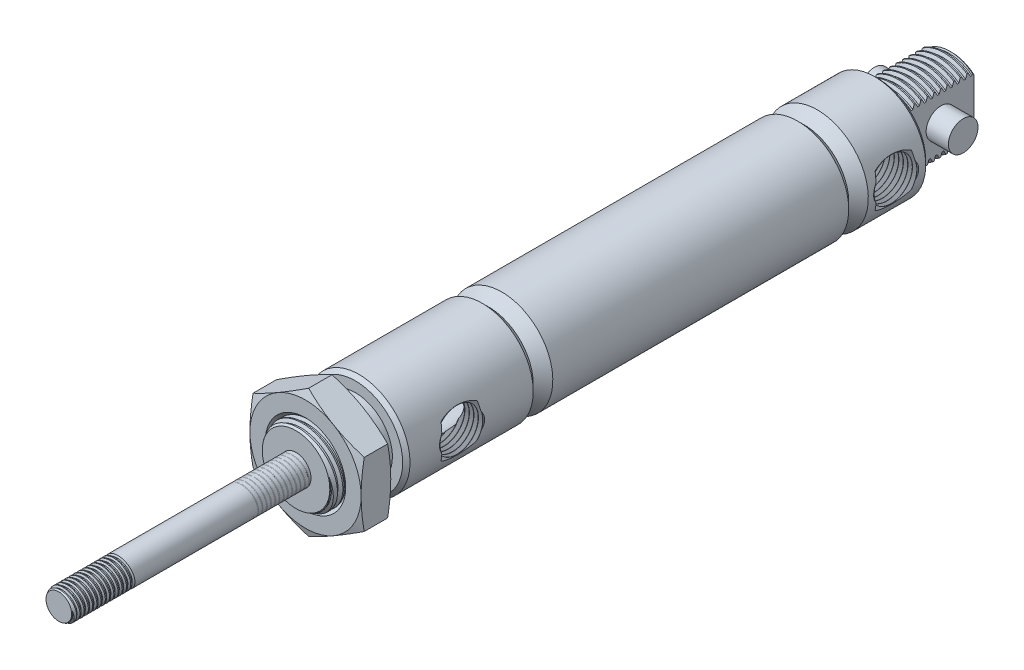
SolidWorks part; units mm, degrees
ref_plane "Front" through (0, 0, 0) normal (0, 0, 1) x (1, 0, 0)
ref_plane "Top" through (0, 0, 0) normal (0, 1, 0) x (1, 0, 0)
ref_plane "Right" through (0, 0, 0) normal (1, 0, 0) x (0, 0, -1)
sketch "Sketch1" plane through (0, 0, 0) normal (1, 0, 0) x (0, 0, -1)
  line L0 (-76.581, 0) -> (76.581, 0) construction
  line L1 (-63.881, -7.9375) -> (-63.881, 0) construction
  line L2 (-63.881, 7.9375) -> (-51.181, 7.9375) construction
  line L3 (-51.181, 0) -> (-51.181, 10.922)
  line L4 (-51.181, 10.922) -> (76.581, 10.922)
  line L5 (60.833, 10.922) -> (60.833, 7.9375) construction
  line L6 (60.833, 7.9375) -> (76.581, 7.9375) construction
  line L7 (76.581, 10.922) -> (76.581, 0)
  line L8 (76.581, 0) -> (92.329, 0) construction
  line L9 (-63.881, -7.9375) -> (-51.181, -7.9375) construction
  line L10 (-51.181, -7.9375) -> (-51.181, -10.922) construction
  line L11 (-51.181, -10.922) -> (76.581, -10.922) construction
  line L12 (60.833, -10.922) -> (60.833, -7.9375) construction
  line L13 (60.833, -7.9375) -> (76.581, -7.9375) construction
  line L14 (-53.467, 9.525) -> (-53.467, 0) construction
  line L18 (-63.881, 3.175) -> (-76.581, 3.175) construction
  line L19 (-76.581, 3.175) -> (-76.581, -3.175) construction
  line L20 (-76.581, -3.175) -> (-63.881, -3.175) construction
  line L24 (-63.881, 4.7625) -> (-53.467, 4.7625) construction
  line L25 (76.581, 0) -> (76.581, -10.922) construction
  line L26 (-63.881, 0) -> (-63.881, 7.9375) construction
  line L28 (-51.181, 0) -> (76.581, 0)
  line L29 (-58.674, 4.7625) -> (-58.674, 7.9375) construction
  line L30 (-51.181, 9.525) -> (-53.467, 9.525) construction
  dimension "D1" = 19.05
  dimension "J Flat" = 15.875
  dimension "E OD" = 21.844
  dimension "K Flat Depth" = 15.748
  dimension "RM Pilot" = 15.875
  dimension "G Pilot Length" = 12.7
  dimension "Shaft Dia" = 6.35
  dimension "A Thread Length" = 12.7
  dimension "Total Length" = 153.162
  dimension "V Pilot Length" = 2.286
revolve "Revolve1" add sketch "Sketch1" angle 360 about L8 reverse direction yes
sketch "Sketch58" plane through (0, 0, 0) normal (1, 0, 0) x (0, 0, -1)
  line L0 (76.581, 0) -> (92.329, 0) construction
  line L1 (60.833, 10.922) -> (76.581, 10.922)
  line L2 (60.833, 10.922) -> (60.833, 7.9375)
  line L3 (60.833, 7.9375) -> (76.581, 7.9375)
  line L4 (76.581, 10.922) -> (76.581, 7.9375)
  line L5 (76.581, 0) -> (92.329, 0) construction
revolve "Cut-Revolve25" cut sketch "Sketch58" angle 360 about L5
sketch "Sketch59" plane through (0, 0, -76.581) normal (0, 0, -1) x (-1, 0, 0)
  line L0 (-4.7625, -7.9375) -> (4.7625, 7.9375) construction
  line L1 (-4.7625, 7.9375) -> (4.7625, 7.9375)
  line L2 (-4.7625, 7.9375) -> (-4.7625, -7.9375)
  line L3 (-4.7625, -7.9375) -> (4.7625, -7.9375)
  line L4 (4.7625, 7.9375) -> (4.7625, -7.9375)
  dimension "D1" = 9.525
extrude "Cut-Extrude3" cut sketch "Sketch59" against normal up to surface (15.748 mm away) flip side to cut up to face at (7.9375, 0, -60.833)
chamfer "Chamfer1" distance 0.7874 angle 45 4 edges at (-10.922, 0, 51.181) (10.922, 0, -60.833) (0, 7.9375, -76.581) (0, -7.9375, -76.581)
sketch "Sketch4" plane through (0, 0, 0) normal (1, 0, 0) x (0, 0, -1)
  line L0 (-63.881, 0) -> (-63.881, 7.9375) construction
  line L1 (-76.581, 0) -> (76.581, 0) construction
  line L2 (-51.181, 0) -> (-51.181, 10.922) construction
  line L3 (-63.881, 7.9375) -> (-51.181, 7.9375) construction
  line L4 (-63.881, 0) -> (-63.881, 7.9375)
  line L5 (-63.881, 0) -> (-51.181, 0)
  line L6 (-51.181, 0) -> (-51.181, 7.9375)
  line L7 (-63.881, 7.9375) -> (-51.181, 7.9375)
  line L8 (-63.881, -7.9375) -> (-51.181, -7.9375) construction
  line L9 (-63.881, -7.9375) -> (-51.181, -7.9375) construction
revolve "Revolve2" add sketch "Sketch4" angle 360 about L5
sketch "Sketch5" plane through (0, 0, 0) normal (1, 0, 0) x (0, 0, -1)
  line L0 (-63.881, 7.9375) -> (-63.881, -7.9375) construction
  line L1 (-63.881, -7.9375) -> (-62.4699, -7.9375) construction
  line L2 (-62.4699, -7.9375) -> (-63.881, 7.9375) construction
  line L3 (-63.881, 7.9375) -> (-63.7053, 7.9531) construction
  line L4 (-63.7053, 7.9531) -> (-62.4754, 8.0624)
  line L5 (-62.4754, 8.0624) -> (-62.847, 7.2626)
  line L6 (-62.847, 7.2626) -> (-63.1984, 7.2314)
  line L7 (-63.1984, 7.2314) -> (-63.7053, 7.9531)
  line L8 (-63.0904, 8.0078) -> (-63.0227, 7.247) construction
  line L9 (-63.881, 7.9375) -> (-63.0841, 7.9375) construction
  line L10 (-63.0841, 7.9375) -> (-61.673, -7.9375) construction
  line L11 (-61.673, -7.9375) -> (-62.4699, -7.9375) construction
  line L12 (-63.881, 0) -> (-63.881, 7.9375) construction
  line L13 (-63.881, 7.9375) -> (-51.181, 7.9375) construction
  line L14 (-63.881, -7.9375) -> (-51.181, -7.9375) construction
  line L15 (-63.881, -0.1335) -> (-60.8761, 0.1335) construction
  point P19 (-62.3786, 0)
  dimension "D1" = 0.1764
  dimension "D2" = 0.3528
  dimension "Thread Pitch" = 1.4111
  dimension "D4" = 60
  dimension "D5" = 1.4111
revolve "Cut-Revolve2" cut sketch "Sketch5" angle 360 about L15
sketch "Sketch6" plane through (0, 0, 0) normal (1, 0, 0) x (0, 0, -1)
  line L0 (-63.881, 7.2314) -> (-62.658, 7.9375)
  line L1 (-62.658, 7.9375) -> (-63.881, 7.9375)
  line L2 (-63.881, 7.9375) -> (-63.881, 7.2314)
  line L3 (0, 0) -> (-63.881, 0) construction
  line L4 (-63.881, 0) -> (-63.881, 7.2314) construction
  line L5 (-63.881, 7.9375) -> (-51.181, 7.9375) construction
  line L6 (-63.881, 0) -> (-63.881, 7.9375) construction
  line L7 (-63.1984, 7.2314) -> (-63.881, 7.2314) construction
  dimension "D1" = 60
revolve "Cut-Revolve3" cut sketch "Sketch6" angle 360 about L3
pattern_linear "LPattern2" count 2 spacing 1.4111 along (0, 0, 1) count 9 spacing 1.4111 along (0, 0, -1) of "Cut-Revolve2"
sketch "Sketch53" plane through (0, 0, 0) normal (1, 0, 0) x (0, 0, -1)
  line L0 (-63.881, 0) -> (-51.181, 0) construction
  line L1 (-51.181, 7.9375) -> (-53.467, 7.9375)
  line L2 (-51.181, 7.9375) -> (-51.181, 0)
  line L3 (-51.181, 0) -> (-53.467, 0)
  line L4 (-53.467, 7.9375) -> (-53.467, 0)
  line L5 (-53.467, 9.525) -> (-53.467, 0) construction
  line L6 (-63.881, 7.9375) -> (-51.181, 7.9375) construction
  line L7 (-51.181, 0) -> (-51.181, 10.922) construction
revolve "Revolve4" add sketch "Sketch53" angle 360 about L3
sketch "Sketch62" plane through (0, 0, 0) normal (1, 0, 0) x (0, 0, -1)
  line L0 (60.833, 7.9375) -> (60.833, -7.9375) construction
  line L1 (60.833, -7.9375) -> (62.2441, -7.9375) construction
  line L2 (62.2441, -7.9375) -> (60.833, 7.9375) construction
  line L3 (60.833, 7.9375) -> (61.0087, 7.9531) construction
  line L4 (61.0087, 7.9531) -> (62.2386, 8.0624)
  line L5 (62.2386, 8.0624) -> (61.867, 7.2626)
  line L6 (61.867, 7.2626) -> (61.5156, 7.2314)
  line L7 (61.5156, 7.2314) -> (61.0087, 7.9531)
  line L8 (61.6913, 7.247) -> (61.6236, 8.0078) construction
  line L9 (60.833, 7.9375) -> (61.6299, 7.9375) construction
  line L10 (61.6299, 7.9375) -> (63.041, -7.9375) construction
  line L11 (63.041, -7.9375) -> (62.2441, -7.9375) construction
  line L12 (60.833, -0.1335) -> (63.8379, 0.1335) construction
  line L13 (60.833, 7.9375) -> (76.581, 7.9375) construction
  line L14 (60.833, 10.922) -> (60.833, 7.9375) construction
  line L15 (60.833, -7.9375) -> (76.581, -7.9375) construction
  point P13 (62.3354, 0)
  dimension "D1" = 60
  dimension "D2" = 0.3528
  dimension "D3" = 0.1764
  dimension "D4" = 1.4111
  dimension "D5" = 1.4111
revolve "Cut-Revolve26" cut sketch "Sketch62" angle 360 about L12
pattern_linear "LPattern5" count 11 spacing 1.4111 along (0, 0, -1) of "Cut-Revolve26"
sketch "Sketch60" plane through (0, 0, 0) normal (1, 0, 0) x (0, 0, -1)
  line L0 (-51.181, 0) -> (76.581, 0) construction
  line L1 (76.581, 10.922) -> (76.581, 0) construction
  circle A0 centre (69.469, 0) radius 3.175
  dimension "D2" = 6.35
  dimension "D1" = 7.112
extrude "Extrude2" add sketch "Sketch60" along normal mid plane 19.05
sketch "Sketch7" plane through (0, 0, 0) normal (1, 0, 0) x (0, 0, -1)
  line L0 (-63.881, 3.2004) -> (-48.006, 3.2004)
  line L1 (-48.006, 3.2004) -> (-48.006, 6.3627)
  line L2 (-48.006, 9.525) -> (-5.842, 9.525) construction
  line L3 (0.508, 9.525) -> (38.608, 9.525)
  line L4 (38.608, 0) -> (-63.881, 0)
  line L5 (-63.881, 0) -> (-63.881, 3.2004)
  line L6 (-63.881, 0) -> (-63.881, 7.9375) construction
  line L7 (-51.181, 0) -> (76.581, 0) construction
  line L8 (38.608, 0) -> (92.329, 0) construction
  line L9 (-51.181, 0) -> (-51.181, 10.922) construction
  line L10 (38.608, 9.525) -> (38.608, 0)
  line L11 (43.561, 10.922) -> (44.958, 9.525)
  line L12 (-48.006, 6.3627) -> (-5.842, 6.3627)
  line L13 (-5.842, 6.3627) -> (-5.842, 9.525)
  line L14 (-48.006, 6.3627) -> (-48.006, 9.525) construction
  line L15 (-5.842, 9.525) -> (0.508, 9.525)
  line L17 (44.958, 9.525) -> (44.958, 8.128)
  line L18 (44.958, 8.128) -> (47.752, 10.922)
  line L19 (47.752, 10.922) -> (43.561, 10.922)
  line L20 (44.958, 9.525) -> (44.958, 10.922) construction
  line L21 (-51.181, 10.922) -> (76.581, 10.922) construction
  line L22 (60.833, 10.922) -> (60.833, 7.9375) construction
  line L23 (-24.003, 10.922) -> (-22.606, 9.525)
  line L24 (-22.606, 9.525) -> (-22.606, 8.128)
  line L25 (-22.606, 8.128) -> (-19.812, 10.922)
  line L26 (-19.812, 10.922) -> (-24.003, 10.922)
  line L27 (-22.606, 9.525) -> (-22.606, 10.922) construction
  line L28 (-63.881, 3.175) -> (-76.581, 3.175) construction
  dimension "D1" = 0.0254
  dimension "Bore Dia" = 19.05
  dimension "D2" = 6.35
  dimension "D3" = 45
  dimension "Stroke" = 38.1
  dimension "D4" = 3.175
  dimension "D5" = 6.35
  dimension "D6" = 15.875
  dimension "D7" = 28.575
revolve "Cut-Revolve5" cut sketch "Sketch7" angle 360 about L8
sketch "Sketch8" plane through (0, 0, 0) normal (1, 0, 0) x (0, 0, -1)
  line L2 (32.258, 9.4742) -> (38.608, 9.4742)
  line L3 (38.608, 9.4742) -> (38.608, 0)
  line L4 (-76.581, 3.175) -> (-76.581, -3.175) construction
  line L6 (-76.581, 3.175) -> (-76.581, 0)
  line L7 (38.608, 0) -> (-76.581, 0)
  line L8 (-76.581, 0) -> (76.581, 0) construction
  line L9 (0.508, 9.525) -> (38.608, 9.525) construction
  line L11 (38.608, 9.525) -> (38.608, 0) construction
  line L15 (32.258, 3.175) -> (32.258, 9.4742)
  line L16 (32.258, 3.175) -> (-76.581, 3.175)
  dimension "D1" = 0.0508
  dimension "D2" = 6.35
revolve "Revolve3" add sketch "Sketch8" angle 360 about L7
sketch "Sketch10" plane through (0, 0, 0) normal (1, 0, 0) x (0, 0, -1)
  line L0 (-76.581, 3.175) -> (-76.581, -3.175) construction
  line L1 (-76.581, -3.175) -> (-75.6739, -3.175) construction
  line L2 (-75.6739, -3.175) -> (-76.581, 3.175) construction
  line L3 (-76.581, 3.175) -> (-76.4687, 3.191) construction
  line L4 (-76.4687, 3.191) -> (-75.683, 3.3033)
  line L5 (-75.683, 3.3033) -> (-75.8942, 2.7771)
  line L6 (-75.8942, 2.7771) -> (-76.1187, 2.7451)
  line L7 (-76.1187, 2.7451) -> (-76.4687, 3.191)
  line L8 (-76.0759, 3.2472) -> (-76.0064, 2.7611) construction
  line L9 (-76.581, 3.175) -> (-76.0656, 3.175) construction
  line L10 (-76.0656, 3.175) -> (-75.1584, -3.175) construction
  line L11 (-75.1584, -3.175) -> (-75.6739, -3.175) construction
  line L12 (-76.581, 3.175) -> (-76.581, -3.175) construction
  line L13 (-63.881, 3.175) -> (-76.581, 3.175) construction
  line L14 (-76.581, -3.175) -> (-63.881, -3.175) construction
  line L15 (-76.581, -0.1384) -> (-74.643, 0.1384) construction
  point P19 (-75.612, 0)
  dimension "D1" = 0.1134
  dimension "D2" = 0.2268
  dimension "Shaft Thread Pitch" = 0.9071
  dimension "D4" = 0.9071
  dimension "D5" = 60
revolve "Cut-Revolve6" cut sketch "Sketch10" angle 360 about L15
sketch "Sketch11" plane through (0, 0, 0) normal (1, 0, 0) x (0, 0, -1)
  line L0 (-76.581, 3.175) -> (-75.8363, 3.175)
  line L1 (-75.8363, 3.175) -> (-76.581, 2.7451)
  line L2 (-76.581, 2.7451) -> (-76.581, 3.175)
  line L3 (0, 0) -> (-76.581, 0) construction
  line L4 (-76.581, 0) -> (-76.581, 2.7451) construction
  line L5 (-63.881, 3.175) -> (-76.581, 3.175) construction
  line L6 (-76.581, 3.175) -> (-76.581, -3.175) construction
  line L7 (-76.1187, 2.7451) -> (-76.581, 2.7451) construction
  dimension "D1" = 30
revolve "Cut-Revolve7" cut sketch "Sketch11" angle 360 about L3
pattern_linear "LPattern3" count 2 spacing 0.9071 along (0, 0, 1) count 14 spacing 0.9071 along (0, 0, -1) of "Cut-Revolve6"
pattern_linear "LPattern4" count 2 spacing 38.1 along (0, 0, 1) of bodies 122
ref_plane "Plane4" through (0, 0, -53.721) normal (0, 0, -1) x (-1, 0, 0)
ref_axis "Axis3" through (0, -15.123, -53.721) along (0, 1, 0)
ref_plane "Plane6" through (0, 0, -53.721) normal (0, 0, 1) x (1, 0, 0)
sketch "Sketch13" plane through (-356.4319, -1.7517, -53.721) normal (0, 0, 1) x (1, 0, 0)
  line L0 (355.9239, 1.7517) -> (355.9239, 5.9543)
  line L1 (355.9239, 5.9543) -> (356.3686, 6.7833) construction
  line L2 (356.3686, 6.7833) -> (356.8642, 5.9837) construction
  line L3 (356.8642, 5.9837) -> (357.3089, 6.8127) construction
  line L4 (357.3089, 6.8127) -> (357.8045, 6.013) construction
  line L5 (356.8811, 6.0153) -> (357.2919, 6.781)
  line L6 (357.2919, 6.781) -> (357.3278, 6.7822)
  line L7 (357.3278, 6.7822) -> (357.7856, 6.0435)
  line L8 (357.7856, 6.0435) -> (357.8214, 6.0446)
  line L9 (355.9239, 5.9543) -> (357.8045, 6.013) construction
  line L10 (356.3686, 6.7833) -> (357.3089, 6.8127) construction
  line L11 (356.1462, 6.3688) -> (357.5567, 6.4128) construction
  line L12 (355.9239, 1.7517) -> (351.7213, 1.7517) construction
  line L13 (357.8214, 6.0446) -> (358.2322, 6.8104)
  line L14 (355.9409, 5.9859) -> (356.3516, 6.7517)
  line L15 (356.3516, 6.7517) -> (356.3875, 6.7528)
  line L16 (356.3875, 6.7528) -> (356.8453, 6.0141)
  line L17 (356.8453, 6.0141) -> (356.8811, 6.0153)
  line L18 (356.1462, 6.3688) -> (355.9239, 6.3618) construction
  line L19 (355.9239, 6.3618) -> (355.9239, 5.9543) construction
  line L20 (356.1462, -2.8653) -> (355.9239, -2.8584) construction
  line L21 (355.9409, 5.9859) -> (355.9239, 5.9543)
  line L22 (358.2322, 6.8104) -> (358.268, 6.8116)
  line L23 (358.268, 6.8116) -> (358.7258, 6.0729)
  line L24 (358.7258, 6.0729) -> (358.7617, 6.074)
  line L25 (358.7617, 6.074) -> (359.1725, 6.8398)
  line L26 (359.1725, 6.8398) -> (359.2083, 6.8409)
  line L27 (359.2083, 6.8409) -> (359.6661, 6.1023)
  line L28 (359.6661, 6.1023) -> (359.702, 6.1034)
  line L29 (359.702, 6.1034) -> (360.1128, 6.8692)
  line L30 (360.1128, 6.8692) -> (360.1486, 6.8703)
  line L31 (360.1486, 6.8703) -> (360.6064, 6.1317)
  line L32 (360.6064, 6.1317) -> (360.6423, 6.1328)
  line L33 (360.6423, 6.1328) -> (361.053, 6.8986)
  line L34 (361.053, 6.8986) -> (361.0889, 6.8997)
  line L35 (361.0889, 6.8997) -> (361.5467, 6.1611)
  line L36 (361.5467, 6.1611) -> (361.5825, 6.1622)
  line L37 (361.5825, 6.1622) -> (361.9933, 6.928)
  line L38 (361.9933, 6.928) -> (362.0292, 6.9291)
  line L39 (362.0292, 6.9291) -> (362.487, 6.1904)
  line L40 (362.487, 6.1904) -> (362.5228, 6.1916)
  line L41 (362.5228, 6.1916) -> (362.9336, 6.9574)
  line L42 (362.9336, 6.9574) -> (362.9695, 6.9585)
  line L43 (362.9695, 6.9585) -> (363.4273, 6.2198)
  line L44 (363.4273, 6.2198) -> (363.4631, 6.221)
  line L45 (363.4631, 6.221) -> (363.8739, 6.9867)
  line L46 (363.8739, 6.9867) -> (363.9097, 6.9879)
  line L47 (363.9097, 6.9879) -> (364.3675, 6.2492)
  line L48 (364.3675, 6.2492) -> (364.4034, 6.2503)
  line L49 (364.4034, 6.2503) -> (364.8142, 7.0161)
  line L50 (364.8142, 7.0161) -> (364.85, 7.0173)
  line L51 (364.85, 7.0173) -> (365.3078, 6.2786)
  line L52 (365.3078, 6.2786) -> (365.3437, 6.2797)
  line L53 (365.3437, 6.2797) -> (365.7545, 7.0455)
  line L54 (365.7545, 7.0455) -> (365.7903, 7.0466)
  line L55 (365.7903, 7.0466) -> (366.2481, 6.308)
  line L56 (366.2481, 6.308) -> (366.284, 6.3091)
  line L57 (366.284, 6.3091) -> (366.6947, 7.0749)
  line L58 (366.6947, 7.0749) -> (366.7306, 7.076)
  line L59 (366.7306, 7.076) -> (367.1884, 6.3374)
  line L60 (367.1884, 6.3374) -> (367.2242, 6.3385)
  line L61 (367.2242, 6.3385) -> (367.635, 7.1043)
  line L62 (367.635, 7.1043) -> (367.6709, 7.1054)
  line L63 (367.6709, 7.1054) -> (368.1287, 6.3668)
  line L64 (368.1287, 6.3668) -> (368.1645, 6.3679)
  line L65 (368.1645, 6.3679) -> (368.5753, 7.1337)
  line L66 (368.5753, 7.1337) -> (368.6111, 7.1348)
  line L67 (368.6111, 7.1348) -> (369.0689, 6.3961)
  line L68 (369.0689, 6.3961) -> (369.1048, 6.3973)
  line L69 (369.1048, 6.3973) -> (369.5156, 7.1631)
  line L70 (369.5156, 7.1631) -> (369.5514, 7.1642)
  line L71 (369.5514, 7.1642) -> (370.0092, 6.4255)
  line L72 (370.0092, 6.4255) -> (370.0451, 6.4267)
  line L73 (355.9239, 1.7517) -> (370.0451, 1.7517)
  line L74 (370.0451, 1.7517) -> (370.0451, 6.4267)
  line L75 (356.3696, 6.7522) -> (356.3686, 6.7833) construction
  line L80 (356.4319, 1.7517) -> (367.3539, 1.7517) construction
  circle A0 centre (356.4319, 1.7517) radius 10.922 construction
  circle A1 centre (356.4319, 1.7517) radius 10.922 construction
  dimension "D1" = 60
  dimension "D2" = 0.031
  dimension "E0" = 9.2202
  dimension "D3" = 0.0359
  dimension "Thread Pitch" = 0.9407
  dimension "Thread Taper" = 3.58
  dimension "L4 Thread Length" = 11.43
revolve "Cut-Revolve22" cut sketch "Sketch13" angle 360 about L12
ref_plane "Plane7" through (0, 0, 39.243) normal (0, 0, 1) x (1, 0, 0)
sketch "Sketch64" plane through (-356.4319, -1.7517, 39.243) normal (0, 0, 1) x (1, 0, 0)
  line L0 (355.9239, 1.7517) -> (355.9239, 5.9543)
  line L1 (355.9239, 5.9543) -> (356.3686, 6.7833) construction
  line L2 (356.3686, 6.7833) -> (356.8642, 5.9837) construction
  line L3 (356.8642, 5.9837) -> (357.3089, 6.8127) construction
  line L4 (357.3089, 6.8127) -> (357.8045, 6.013) construction
  line L5 (356.8896, 6.0311) -> (357.2834, 6.7652)
  line L6 (357.2834, 6.7652) -> (357.3372, 6.7669)
  line L7 (357.3372, 6.7669) -> (357.7761, 6.0588)
  line L8 (357.7761, 6.0588) -> (357.8299, 6.0604)
  line L9 (355.9239, 5.9543) -> (357.8045, 6.013) construction
  line L10 (356.3686, 6.7833) -> (357.3089, 6.8127) construction
  line L11 (356.1462, 6.3688) -> (357.5567, 6.4128) construction
  line L12 (355.9239, 1.7517) -> (351.7213, 1.7517) construction
  line L13 (357.8299, 6.0604) -> (358.2237, 6.7946)
  line L14 (355.9493, 6.0017) -> (356.3432, 6.7359)
  line L15 (356.3432, 6.7359) -> (356.3969, 6.7375)
  line L16 (356.3969, 6.7375) -> (356.8358, 6.0294)
  line L17 (356.8358, 6.0294) -> (356.8896, 6.0311)
  line L18 (356.1462, 6.3688) -> (355.9239, 6.3618) construction
  line L19 (355.9239, 6.3618) -> (355.9239, 5.9543) construction
  line L20 (356.1462, -2.8653) -> (355.9239, -2.8584) construction
  line L21 (355.9493, 6.0017) -> (355.9239, 5.9543)
  line L22 (358.2237, 6.7946) -> (358.2775, 6.7963)
  line L23 (358.2775, 6.7963) -> (358.7164, 6.0882)
  line L24 (358.7164, 6.0882) -> (358.7702, 6.0898)
  line L25 (358.7702, 6.0898) -> (359.164, 6.824)
  line L26 (359.164, 6.824) -> (359.2178, 6.8257)
  line L27 (359.2178, 6.8257) -> (359.6567, 6.1175)
  line L28 (359.6567, 6.1175) -> (359.7105, 6.1192)
  line L29 (359.7105, 6.1192) -> (360.1043, 6.8534)
  line L30 (360.1043, 6.8534) -> (360.1581, 6.8551)
  line L31 (360.1581, 6.8551) -> (360.597, 6.1469)
  line L32 (360.597, 6.1469) -> (360.6507, 6.1486)
  line L33 (360.6507, 6.1486) -> (361.0446, 6.8828)
  line L34 (361.0446, 6.8828) -> (361.0983, 6.8845)
  line L35 (361.0983, 6.8845) -> (361.5372, 6.1763)
  line L36 (361.5372, 6.1763) -> (361.591, 6.178)
  line L37 (361.591, 6.178) -> (361.9849, 6.9122)
  line L38 (361.9849, 6.9122) -> (362.0386, 6.9139)
  line L39 (362.0386, 6.9139) -> (362.4775, 6.2057)
  line L40 (362.4775, 6.2057) -> (362.5313, 6.2074)
  line L41 (362.5313, 6.2074) -> (362.9251, 6.9416)
  line L42 (362.9251, 6.9416) -> (362.9789, 6.9432)
  line L43 (362.9789, 6.9432) -> (363.4178, 6.2351)
  line L44 (363.4178, 6.2351) -> (363.4716, 6.2368)
  line L45 (363.4716, 6.2368) -> (363.8654, 6.9709)
  line L46 (363.8654, 6.9709) -> (363.9192, 6.9726)
  line L47 (363.9192, 6.9726) -> (364.3581, 6.2645)
  line L48 (364.3581, 6.2645) -> (364.4119, 6.2661)
  line L49 (364.4119, 6.2661) -> (364.8057, 7.0003)
  line L50 (364.8057, 7.0003) -> (364.8595, 7.002)
  line L51 (364.8595, 7.002) -> (365.2984, 6.2938)
  line L52 (365.2984, 6.2938) -> (365.3521, 6.2955)
  line L53 (365.3521, 6.2955) -> (365.746, 7.0297)
  line L54 (365.746, 7.0297) -> (365.7997, 7.0314)
  line L55 (365.7997, 7.0314) -> (366.2387, 6.3232)
  line L56 (366.2387, 6.3232) -> (366.2924, 6.3249)
  line L57 (366.2924, 6.3249) -> (366.6863, 7.0591)
  line L58 (366.6863, 7.0591) -> (366.74, 7.0608)
  line L59 (366.74, 7.0608) -> (367.1789, 6.3526)
  line L60 (367.1789, 6.3526) -> (367.2327, 6.3543)
  line L61 (367.2327, 6.3543) -> (367.6265, 7.0885)
  line L62 (367.6265, 7.0885) -> (367.6803, 7.0902)
  line L63 (367.6803, 7.0902) -> (368.1192, 6.382)
  line L64 (368.1192, 6.382) -> (368.173, 6.3837)
  line L65 (368.173, 6.3837) -> (368.5668, 7.1179)
  line L66 (368.5668, 7.1179) -> (368.6206, 7.1196)
  line L67 (368.6206, 7.1196) -> (369.0595, 6.4114)
  line L68 (369.0595, 6.4114) -> (369.1133, 6.4131)
  line L69 (369.1133, 6.4131) -> (369.5071, 7.1473)
  line L70 (369.5071, 7.1473) -> (369.5609, 7.1489)
  line L71 (369.5609, 7.1489) -> (369.9998, 6.4408)
  line L72 (369.9998, 6.4408) -> (370.0536, 6.4425)
  line L73 (355.9239, 1.7517) -> (370.0536, 1.7517)
  line L74 (370.0536, 1.7517) -> (370.0536, 6.4425)
  line L75 (356.37, 6.7367) -> (356.3686, 6.7833) construction
  line L80 (356.4319, 1.7517) -> (367.3539, 1.7517) construction
  circle A1 centre (356.4319, 1.7517) radius 10.922 construction
  circle A2 centre (356.4319, 1.7517) radius 10.922 construction
  dimension "D1" = 60
  dimension "D2" = 0.0466
  dimension "D3" = 0.0538
  dimension "Thread Pitch" = 0.9407
  dimension "D4" = 9.2202
  dimension "Thread Taper" = 3.58
  dimension "L4 Thread Length" = 11.43
revolve "Cut-Revolve27" cut sketch "Sketch64" angle 360 about L73
ref_plane "Plane2" through (0, 0, 58.674) normal (0, 0, 1) x (1, 0, 0)
sketch "Sketch54" plane through (0, 0, 58.674) normal (0, 0, 1) x (1, 0, 0)
  line L1 (0, 13.7482) -> (-11.9062, 6.8741)
  line L2 (-11.9062, 6.8741) -> (-11.9062, -6.8741)
  line L3 (-11.9062, -6.8741) -> (0, -13.7482)
  line L4 (0, -13.7482) -> (11.9062, -6.8741)
  line L5 (11.9062, -6.8741) -> (11.9062, 6.8741)
  line L6 (11.9062, 6.8741) -> (0, 13.7482)
  circle A0 centre (0, 0) radius 11.9062 construction
  circle A1 centre (0, 0) radius 7.9375
  dimension "Nut Hex" = 23.8125
extrude "Extrude1" add sketch "Sketch54" along normal mid plane 6.35 separate body
sketch "Sketch55" plane through (0, 0, 0) normal (1, 0, 0) x (0, 0, -1)
  line L0 (-61.1786, 13.7482) -> (-61.849, 13.7482)
  line L1 (-61.849, 13.7482) -> (-61.849, 11.9062)
  line L2 (-61.849, 11.9062) -> (-61.1786, 13.7482)
  line L3 (-56.1694, 13.7482) -> (-55.499, 13.7482)
  line L4 (-55.499, 13.7482) -> (-55.499, 11.9062)
  line L5 (-55.499, 11.9062) -> (-56.1694, 13.7482)
  line L6 (-61.849, 11.9062) -> (-55.499, 11.9062) construction
  line L7 (-61.849, 13.7482) -> (-55.499, 13.7482) construction
  line L10 (0, 0) -> (-61.849, 0) construction
  line L11 (-61.849, 0) -> (-61.849, 11.9062) construction
  line L12 (-61.849, 8.6079) -> (-61.849, 7.9375)
  line L13 (-61.849, 7.9375) -> (-61.1786, 7.9375)
  line L14 (-61.1786, 7.9375) -> (-61.849, 8.6079)
  line L15 (-55.499, 8.6079) -> (-55.499, 7.9375)
  line L16 (-55.499, 7.9375) -> (-56.1694, 7.9375)
  line L17 (-56.1694, 7.9375) -> (-55.499, 8.6079)
  line L19 (-61.1786, 13.7482) -> (-61.1786, 7.9375) construction
  line L20 (-55.499, 6.8741) -> (-55.499, 13.7482) construction
  line L21 (-61.849, 6.8741) -> (-61.849, 13.7482) construction
  line L22 (-55.499, 7.9375) -> (-61.849, 7.9375) construction
  dimension "D1" = 20
  dimension "D2" = 23.8125
  dimension "D3" = 45
revolve "Cut-Revolve24" cut sketch "Sketch55" angle 360 about L10
equation "\"D1@Chamfer1\"=\"K Flat Depth@Sketch1\"/20"
equation "\"D1@Sketch5\"=\"Thread Pitch@Sketch5\"/8"
equation "\"D2@Sketch5\"=\"Thread Pitch@Sketch5\"/4"
equation "\"D5@Sketch5\"=\"Thread Pitch@Sketch5\""
equation "\"D3@LPattern2\"=\"Thread Pitch@Sketch5\""
equation "\"D4@LPattern2\"=\"Thread Pitch@Sketch5\""
equation "\"D2@LPattern2\"=\"G Pilot Length@Sketch1\"/\"Thread Pitch@Sketch5\""
equation "\"D1@Sketch10\"=\"Shaft Thread Pitch@Sketch10\"/8"
equation "\"D2@Sketch10\"=\"Shaft Thread Pitch@Sketch10\"/4"
equation "\"D4@Sketch10\"=\"Shaft Thread Pitch@Sketch10\""
equation "\"D3@LPattern3\"=\"Shaft Thread Pitch@Sketch10\""
equation "\"D4@LPattern3\"=\"Shaft Thread Pitch@Sketch10\""
equation "\"D2@LPattern3\"=\"A Thread Length@Sketch1\"/\"Shaft Thread Pitch@Sketch10\""
equation "\"D3@LPattern4\"=\"Stroke@Sketch7\""
equation "\"D2@Sketch13\"=\"Thread Pitch@Sketch13\"*.033"
equation "\"D2@Sketch55\"=\"Nut Hex@Sketch54\""
equation "\"D3@Sketch62\"=\"D4@Sketch62\"/8"
equation "\"D2@Sketch62\"=\"D4@Sketch62\"/4"
equation "\"D5@Sketch62\"=\"D4@Sketch62\""
equation "\"D4@Sketch62\"=\"Thread Pitch@Sketch5\""
equation "\"D3@LPattern5\"=\"Thread Pitch@Sketch5\""
equation "\"D1@LPattern5\"=\"K Flat Depth@Sketch1\"/\"Thread Pitch@Sketch5\""
